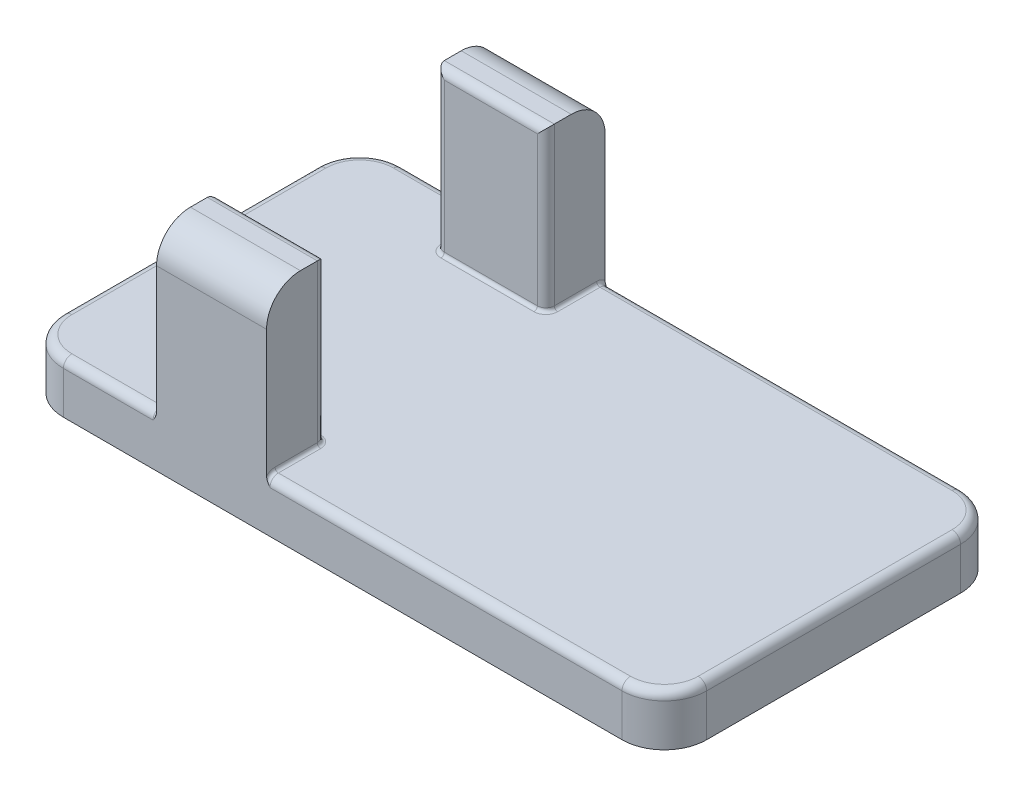
SolidWorks part; units mm, degrees
ref_plane "Спереди" through (0, 0, 0) normal (0, 0, 1) x (1, 0, 0)
ref_plane "Сверху" through (0, 0, 0) normal (0, 1, 0) x (1, 0, 0)
ref_plane "Справа" through (0, 0, 0) normal (1, 0, 0) x (0, 0, -1)
other "Configuration Table"
sketch "Эскиз1" plane through (0, 0, 0) normal (0, 1, 0) x (1, 0, 0)
  line L1 (-38, -20) -> (38, -20)
  line L2 (-38, -20) -> (-38, 20)
  line L3 (-38, 20) -> (38, 20)
  line L4 (38, -20) -> (38, 20)
  line L5 (0, 20) -> (0, -20) construction
  line L6 (-38, 0) -> (38, 0) construction
  point P0 (0, 0)
  dimension "D1" = 76
  dimension "D2" = 40
extrude "Бобышка-Вытянуть1" add sketch "Эскиз1" along normal blind 6
sketch "Эскиз2" plane through (0, 6, 0) normal (0, 1, 0) x (1, 0, 0)
  line L0 (0, 20) -> (0, -20) construction
  line L1 (38, 20) -> (-38, 20) construction
  line L2 (-38, -20) -> (38, -20) construction
  line L3 (-38, 0) -> (38, 0) construction
  line L4 (-38, 20) -> (-38, -20) construction
  line L5 (38, -20) -> (38, 20) construction
  line L7 (-22, -20) -> (-9, -20)
  line L8 (-22, -20) -> (-22, 20)
  line L9 (-22, 20) -> (-9, 20)
  line L10 (-9, -20) -> (-9, 20)
  line L11 (-15.5, 20) -> (-15.5, -20) construction
  line L12 (-22, 0) -> (-9, 0) construction
  point P800 (-15.5, 0)
  dimension "D1" = 9
  dimension "D2" = 13
extrude "Бобышка-Вытянуть2" add sketch "Эскиз2" along normal blind 19
sketch "Эскиз3" plane through (0, 25, 0) normal (0, 1, 0) x (1, 0, 0)
  line L0 (-22, 0) -> (-9, 0) construction
  line L1 (-22, 20) -> (-22, -20) construction
  line L2 (-9, -20) -> (-9, 20) construction
  line L3 (-22, 20) -> (-22, -20) construction
  line L4 (-22, 13) -> (-9, 13)
  line L5 (-22, 13) -> (-22, -13)
  line L6 (-22, -13) -> (-9, -13)
  line L7 (-9, 13) -> (-9, -13)
  line L8 (-15.5, -13) -> (-15.5, 13) construction
  line L9 (-22, 0) -> (-9, 0) construction
  line L10 (-9, -20) -> (-9, 20) construction
  line L11 (-22, -20) -> (-9, -20) construction
  point P234 (-15.5, 0)
  dimension "D1" = 26
  dimension "D2" = 7
extrude "Вырез-Вытянуть1" cut sketch "Эскиз3" against normal blind 19
fillet "Скругление1" radius 4 2 edges at (-15.5, 25, -20) (-15.5, 25, 20)
fillet "Скругление2" radius 1 3 edges at (-9, 15.5, -13) (-22, 15.5, -13) (-15.5, 25, -13)
fillet "Скругление3" radius 1 3 edges at (-9, 15.5, 13) (-15.5, 25, 13) (-22, 15.5, 13)
fillet "Скругление4" radius 5 4 edges at (-38, 3, -20) (-38, 3, 20) (38, 3, 20) (38, 3, -20)
fillet "Скругление5" radius 1 5 edges at (-27.5, 6, -20) (-36.5355, 6, -18.5355) (-38, 6, 0) (-36.5355, 6, 18.5355) (-27.5, 6, 20)
fillet "Скругление6" radius 1 5 edges at (12, 6, -20) (36.5355, 6, -18.5355) (38, 6, 0) (36.5355, 6, 18.5355) (12, 6, 20)
fillet "Скругление7" radius 0.4 14 edges at (-22, 5.7071, -19.7071) (-21.7071, 6, -13.2929) (-15.5, 6, -13) (-9.2929, 6, -13.2929) (-9, 5.7071, -19.7071) (-9, 5.7071, 19.7071) (-22, 5.7071, 19.7071) (-21.7071, 6, 13.2929) (-15.5, 6, 13) (-9.2929, 6, 13.2929) (-22, 6, 16.5) (-22, 6, -16.5) (-9, 6, -16.5) (-9, 6, 16.5)
